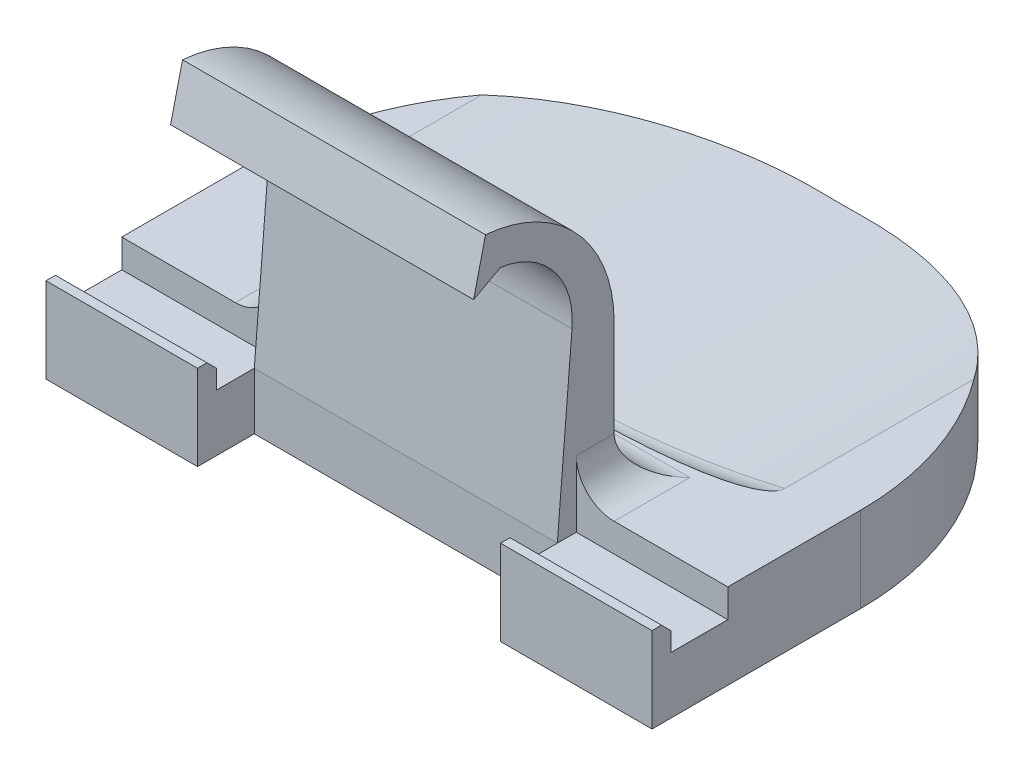
SolidWorks part; units mm, degrees
ref_plane "Спереди" through (0, 0, 0) normal (0, 0, 1) x (1, 0, 0)
ref_plane "Сверху" through (0, 0, 0) normal (0, 1, 0) x (1, 0, 0)
ref_plane "Справа" through (0, 0, 0) normal (1, 0, 0) x (0, 0, -1)
sketch "Эскиз2" plane through (0, 0, 0) normal (0, 1, 0) x (1, 0, 0)
  line L1 (-1, 13) -> (1, 13)
  line L2 (-16, -2) -> (-16, -13)
  line L3 (-16, -13) -> (16, -13)
  line L4 (16, -2) -> (16, -13)
  line L5 (-16, 13) -> (16, -13) construction
  line L6 (-16, -13) -> (16, 13) construction
  arc A0 (1, 13) -> (16, -2) centre (1, -2) cw
  arc A1 (-1, 13) -> (-16, -2) centre (-1, -2) ccw
  point P0 (0, 0)
  dimension "D3" = 15
  dimension "D1" = 26
  dimension "D2" = 32
extrude "Бобышка-Вытянуть1" add sketch "Эскиз2" along normal blind 4.5
sketch "Эскиз3" plane through (0, 4.5, 0) normal (0, 1, 0) x (1, 0, 0)
  line L0 (-16, -2) -> (-16, -13) construction
  line L1 (-16, -12) -> (16, -12)
  line L2 (-16, -12) -> (-16, -9)
  line L3 (-16, -9) -> (16, -9)
  line L4 (16, -12) -> (16, -9)
  line L5 (16, -13) -> (16, -2) construction
  line L6 (-16, -13) -> (16, -13) construction
  dimension "D1" = 3
  dimension "D2" = 1
extrude "Вырез-Вытянуть1" cut sketch "Эскиз3" against normal blind 1.5
sketch "Эскиз4" plane through (0, 0, -13) normal (0, 0, -1) x (-1, 0, 0)
  line L0 (-1, 4.5) -> (-16, 4.5) construction
  line L1 (16, 4.5) -> (1, 4.5) construction
  line L2 (-16, 4.5) -> (-16, 0) construction
  line L3 (16, 4.5) -> (16, 0) construction
  line L4 (-1, 4.5) -> (1, 4.5) construction
  line L5 (-13, 4.5) -> (13, 4.5)
  line L6 (-16, 0) -> (-1, 0) construction
  line L7 (1, 0) -> (16, 0) construction
  line L8 (-13, 0) -> (13, 0)
  arc A0 (-13, 4.5) -> (13, 4.5) centre (0, 60.0833) ccw
  arc A1 (-13, 0) -> (13, 0) centre (0, -55.5833) cw
  point P13 (0, 3)
  point P17 (0, 1.5)
  dimension "D1" = 3
  dimension "D2" = 3
  dimension "D3" = 1.5
  dimension "D4" = 3
  dimension "D5" = 3
  dimension "D6" = 1.5
extrude "Вырез-Вытянуть4" cut sketch "Эскиз4" against normal blind 18
fillet "Скругление1" radius 2 2 edges at (0, 3, 5) (0, 1.5, 5)
sketch "Эскиз5" plane through (0, 0, 0) normal (0, -1, 0) x (1, 0, 0)
  line L0 (-16, 13) -> (16, 13) construction
  line L1 (-16, 2) -> (-16, 13) construction
  line L2 (-8, 13) -> (8, 13)
  line L3 (-8, 13) -> (-8, 10)
  line L4 (-8, 10) -> (8, 10)
  line L5 (8, 13) -> (8, 10)
  line L6 (16, 13) -> (16, 2) construction
  dimension "D1" = 3
  dimension "D2" = 8
  dimension "D3" = 8
extrude "Вырез-Вытянуть5" cut sketch "Эскиз5" against normal blind 5
ref_plane "Плоскость1" through (-8, 0, 0) normal (1, 0, 0) x (0, 0, -1)
sketch "Эскиз7" plane through (-8, 0, 0) normal (1, 0, 0) x (0, 0, -1)
  line L0 (-7, 4.5) -> (-7, 11.6065)
  line L1 (-2, 4.5) -> (-9, 4.5) construction
  line L2 (-10, 3) -> (-7, 3)
  line L3 (-13.7912, 19) -> (-14.4202, 16.3449)
  line L4 (-14.4202, 16.3449) -> (-13, 17.1097)
  line L5 (-10, 3) -> (-9.2252, 12.4123)
  line L6 (-2, 0) -> (-13, 0) construction
  line L7 (-13, 3.4587) -> (-13, 23.8348) construction
  line L8 (-13, 4.5) -> (-13, 0) construction
  line L9 (-7, 3) -> (-7, 4.5)
  arc A0 (-7, 11.6065) -> (-13.7912, 19) centre (-14.4202, 11.6065) ccw
  arc A1 (-9.2252, 12.4123) -> (-13, 17.1097) centre (-13.5885, 12.7714) ccw
  dimension "D1" = 19
  dimension "D2" = 3
  dimension "D3" = 1.8903
  dimension "D4" = 2.6551
extrude "Бобышка-Вытянуть2" add sketch "Эскиз7" along normal blind 16
fillet "Скругление2" radius 2 1 edges at (0, 4.5, 7)
fillet "Скругление3" radius 2 2 edges at (8, 4.5, 7) (-8, 4.5, 7)
chamfer "Фаска1" distance 0.5 angle 45 2 edges at (-12, 4.5, 12) (12, 4.5, 12)
